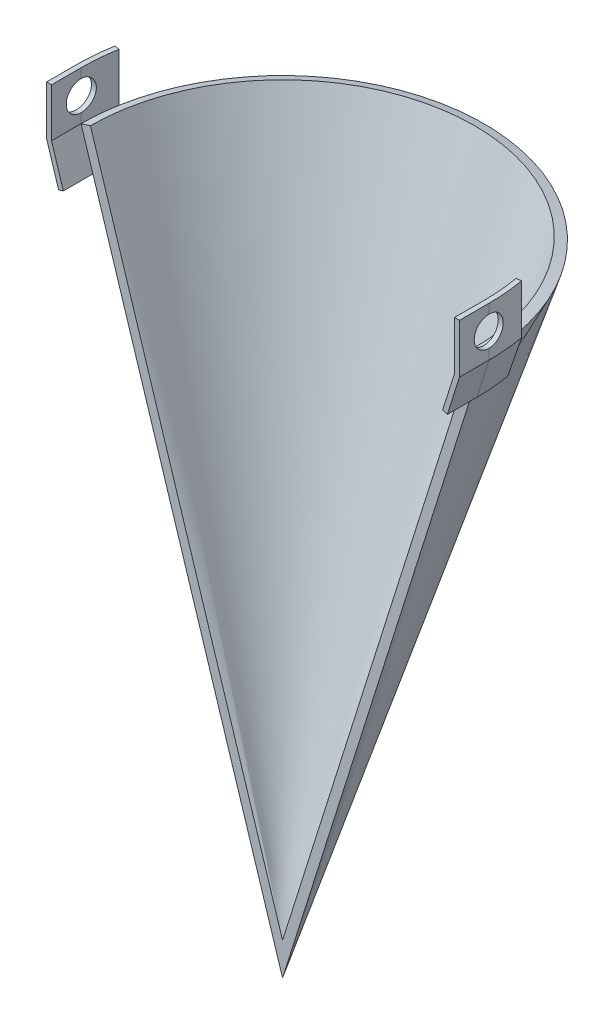
SolidWorks part; units mm, degrees
ref_plane "Alzado" through (0, 0, 0) normal (0, 0, 1) x (1, 0, 0)
ref_plane "Planta" through (0, 0, 0) normal (0, 1, 0) x (1, 0, 0)
ref_plane "Vista lateral" through (0, 0, 0) normal (1, 0, 0) x (0, 0, -1)
sketch "Croquis1" plane through (0, 0, 0) normal (0, 0, 1) x (1, 0, 0)
  line L0 (0, 0) -> (0, 6.651)
  line L1 (0, 6.651) -> (39.0283, 130.4331)
  line L2 (39.0283, 130.4331) -> (40.9358, 129.8317)
  line L3 (40.9358, 129.8317) -> (0, 0)
  line L4 (-39.0283, 130.4331) -> (-40.9358, 129.8317) construction
  line L5 (0, 6.651) -> (-39.0283, 130.4331) construction
  line L6 (-40.9358, 129.8317) -> (0, 0) construction
  ellipse E0 centre (0, 74.8317) end of major axis (0, 99.8317) minor radius 20 construction
  point P6 (0, 0)
  point P12 (0, 0)
  point P13 (0, 0)
  point P14 (0, 0)
  point P15 (0, 23.6332)
  point P18 (0, 77.1537)
  point P19 (54.9723, 105.8772)
  dimension "D1" = 2
  dimension "D2" = 40
  dimension "D3" = 50
  dimension "D4" = 30
  dimension "D5" = 35
revolve "Revolución1" add sketch "Croquis1" angle 180 about L0
sketch "Croquis2" plane through (0, 0, 0) normal (0, 0, 1) x (1, 0, 0)
  line L0 (40.9358, 129.8317) -> (40.9358, 139.6778)
  line L1 (40.9358, 139.6778) -> (41.9358, 139.6778)
  line L2 (41.9358, 139.6778) -> (41.9358, 129.6778)
  line L3 (41.9358, 129.6778) -> (39.4838, 121.9013)
  line L4 (39.4838, 121.9013) -> (38.5301, 122.202)
  line L5 (0, 0) -> (40.9358, 129.8317) construction
  line L6 (38.5301, 122.202) -> (40.9358, 129.8317)
  line L7 (40.9358, 129.8317) -> (39.0283, 130.4331) construction
  line L8 (0, 0) -> (0, 49.932) construction
  dimension "D1" = 1
  dimension "D2" = 8
  dimension "D3" = 10
revolve "Revolución2" add sketch "Croquis2" angle 10 about L8
sketch "Croquis3" plane through (0, 0, 0) normal (0, 0, 1) x (1, 0, 0)
  line L0 (40.9358, 139.6778) -> (41.9358, 139.6778)
  line L1 (41.9358, 139.6778) -> (41.9358, 129.6778)
  line L2 (41.9358, 129.6778) -> (39.4838, 121.9013)
  line L3 (39.4838, 121.9013) -> (38.5301, 122.202)
  line L4 (38.5301, 122.202) -> (40.9358, 129.8317)
  line L5 (40.9358, 129.8317) -> (40.9358, 139.6778)
extrude "Saliente-Extruir1" add sketch "Croquis3" along normal blind 6
sketch "Croquis4" plane through (40.9358, 0, 0) normal (-1, 0, 0) x (0, 0, 1)
  line L3 (0, 139.6778) -> (0, 129.8317) construction
  circle A0 centre (0, 134.7547) radius 3
  point P2 (0, 0)
  point P3 (2.9166, 134.7547)
  point P4 (1.4188, 134.7329)
  point P5 (0, 134.7547)
  point P6 (0, 134.7547)
  dimension "D1" = 6
extrude "Cortar-Extruir1" cut sketch "Croquis4" against normal through all and the other way blind 6
ref_plane "Plano1" through (0, 0, 0) normal (1, 0, 0) x (0, 0, -1)
mirror "Simetría1" about plane through (0, 0, 0) normal (1, 0, 0) of "Cortar-Extruir1", "Revolución2", "Saliente-Extruir1"
